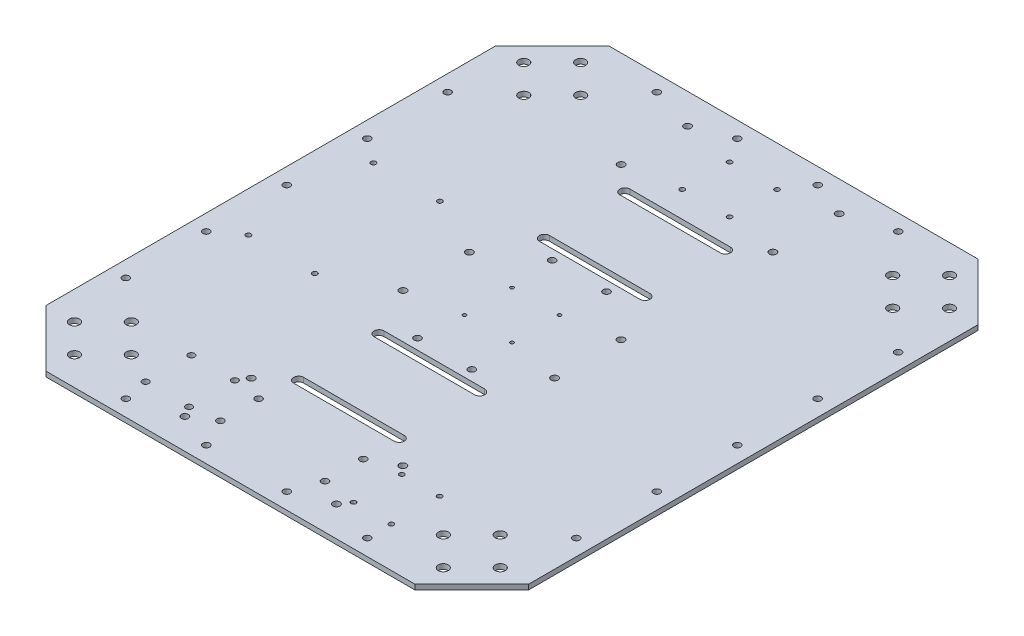
SolidWorks part; units mm, degrees
ref_plane "Front Plane" through (0, 0, 0) normal (0, 0, 1) x (1, 0, 0)
ref_plane "Top Plane" through (0, 0, 0) normal (0, 1, 0) x (1, 0, 0)
ref_plane "Right Plane" through (0, 0, 0) normal (1, 0, 0) x (0, 0, -1)
sketch "Sketch1" plane through (0, 0, 0) normal (0, 1, 0) x (1, 0, 0)
  line L0 (-121.2861, 87.138) -> (-85.365, 123.059)
  line L1 (-121.2861, 123.059) -> (183.5139, 123.059)
  line L2 (-121.2861, 123.059) -> (-121.2861, -232.541)
  line L3 (-121.2861, -232.541) -> (183.5139, -232.541)
  line L4 (183.5139, 123.059) -> (183.5139, -232.541)
  line L5 (31.1139, 95.069) -> (31.1139, -294.9418) construction
  line L6 (-146.0448, -54.741) -> (218.038, -54.741) construction
  line L7 (183.5139, 87.138) -> (147.5929, 123.059)
  line L8 (183.5139, -196.62) -> (147.5929, -232.541)
  line L9 (-121.2861, -196.62) -> (-85.365, -232.541)
  circle A0 centre (-16.7651, 104.009) radius 2.2225
  circle A1 centre (78.9929, 104.009) radius 2.2225
  circle A2 centre (-16.7651, 62.099) radius 2.2225
  circle A3 centre (78.9929, 62.099) radius 2.2225
  circle A4 centre (-16.7651, -171.581) radius 2.2225
  circle A5 centre (78.9929, -171.581) radius 2.2225
  circle A6 centre (78.9929, -213.491) radius 2.2225
  circle A7 centre (-16.7651, -213.491) radius 2.2225
  circle A8 centre (-16.7651, -33.786) radius 2.2225
  circle A9 centre (78.9929, -33.786) radius 2.2225
  circle A10 centre (78.9929, -75.696) radius 2.2225
  circle A11 centre (-16.7651, -75.696) radius 2.2225
  point P8 (31.1139, 123.059)
  point P11 (-121.2861, -54.741)
  dimension "D6" = 95.758
  dimension "D13" = 4.445
  dimension "D1" = 304.8
  dimension "D2" = 355.6
  dimension "D3" = 45
  dimension "D4" = 50.8
  dimension "D5" = 41.91
  dimension "D7" = 104.521
  dimension "D8" = 19.05
  dimension "D9" = 41.91
  dimension "D10" = 20.955
  dimension "D11" = 95.758
  dimension "D12" = 47.879
extrude "Boss-Extrude1" add sketch "Sketch1" along normal blind 3.175 contours L2 L9 L3 L8 L4 L7 L1 L0 region at (31.1139, 0, 54.741)
sketch "Sketch2" plane through (0, 3.175, 0) normal (0, 1, 0) x (1, 0, 0)
  line L0 (31.1139, 123.059) -> (31.1139, -287.8465) construction
  line L1 (-85.365, 123.059) -> (147.5929, 123.059) construction
  line L2 (183.5139, -54.741) -> (-158.2106, -54.741) construction
  line L3 (183.5139, 87.138) -> (183.5139, -196.62) construction
  circle A0 centre (13.8419, -12.069) radius 2.159
  circle A1 centre (48.1319, -12.069) radius 2.159
  circle A2 centre (13.8419, -97.159) radius 2.159
  circle A3 centre (48.1319, -97.159) radius 2.159
  dimension "D5" = 4.318
  dimension "D6" = 4.318
  dimension "D7" = 4.318
  dimension "D8" = 4.318
  dimension "D1" = 17.272
  dimension "D2" = 34.29
  dimension "D3" = 85.09
  dimension "D4" = 42.672
extrude "Cut-Extrude1" cut sketch "Sketch2" against normal through all
sketch "Sketch4" plane through (0, 3.175, 0) normal (0, 1, 0) x (1, 0, 0)
  line L0 (-0.6361, 48.256) -> (62.8639, 48.256) construction
  line L1 (-0.6361, 51.431) -> (62.8639, 51.431)
  line L2 (-0.6361, 45.081) -> (62.8639, 45.081)
  line L3 (-0.6361, -2.544) -> (62.8639, -2.544) construction
  line L4 (-0.6361, 0.631) -> (62.8639, 0.631)
  line L5 (-0.6361, -5.719) -> (62.8639, -5.719)
  line L6 (31.1139, 123.059) -> (31.1139, -75.2432) construction
  line L7 (-85.365, 123.059) -> (147.5929, 123.059) construction
  line L8 (-121.2861, -54.741) -> (257.7387, -54.741) construction
  line L9 (-121.2861, 87.138) -> (-121.2861, -196.62) construction
  line L10 (31.1139, -232.541) -> (31.1139, -34.2388) construction
  line L11 (-0.6361, -106.938) -> (62.8639, -106.938) construction
  line L12 (-0.6361, -110.113) -> (62.8639, -110.113)
  line L13 (-0.6361, -103.763) -> (62.8639, -103.763)
  line L14 (-0.6361, -157.738) -> (62.8639, -157.738) construction
  line L15 (-0.6361, -160.913) -> (62.8639, -160.913)
  line L16 (-0.6361, -154.563) -> (62.8639, -154.563)
  arc A0 (-0.6361, 51.431) -> (-0.6361, 45.081) centre (-0.6361, 48.256) ccw
  arc A1 (62.8639, 45.081) -> (62.8639, 51.431) centre (62.8639, 48.256) ccw
  arc A2 (-0.6361, 0.631) -> (-0.6361, -5.719) centre (-0.6361, -2.544) ccw
  arc A3 (62.8639, -5.719) -> (62.8639, 0.631) centre (62.8639, -2.544) ccw
  circle A4 centre (48.1319, -12.069) radius 2.159 construction
  arc A5 (-0.6361, -110.113) -> (-0.6361, -103.763) centre (-0.6361, -106.938) cw
  arc A6 (62.8639, -103.763) -> (62.8639, -110.113) centre (62.8639, -106.938) cw
  arc A7 (-0.6361, -160.913) -> (-0.6361, -154.563) centre (-0.6361, -157.738) cw
  arc A8 (62.8639, -154.563) -> (62.8639, -160.913) centre (62.8639, -157.738) cw
  point P2 (31.1139, 48.256)
  point P7 (31.1139, -2.544)
  point P28 (31.1139, -106.938)
  point P35 (31.1139, -157.738)
  dimension "D1" = 63.5
  dimension "D2" = 63.5
  dimension "D3" = 6.35
  dimension "D4" = 6.35
  dimension "D5" = 44.45
  dimension "D6" = 6.35
extrude "Cut-Extrude2" cut sketch "Sketch4" against normal through all
sketch "Sketch7" plane through (0, 3.175, 0) normal (0, 1, 0) x (1, 0, 0)
  line L0 (31.1139, 123.059) -> (31.1139, -19.2461) construction
  line L3 (-85.365, 123.059) -> (147.5929, 123.059) construction
  circle A0 centre (16.1279, 67.687) radius 1.524
  circle A1 centre (46.0999, 67.687) radius 1.524
  circle A2 centre (16.1279, 97.659) radius 1.524
  circle A3 centre (46.0999, 97.659) radius 1.524
  dimension "D1" = 3.048
  dimension "D2" = 3.048
  dimension "D4" = 14.986
  dimension "D3" = 29.972
  dimension "D5" = 25.4
extrude "Cut-Extrude3" cut sketch "Sketch7" against normal through all
sketch "Sketch8" plane through (0, 3.175, 0) normal (0, 1, 0) x (1, 0, 0)
  line L0 (-85.365, -232.541) -> (147.5929, -232.541) construction
  line L1 (183.5139, 87.138) -> (183.5139, -196.62) construction
  circle A0 centre (83.4379, -207.141) radius 1.524
  circle A1 centre (83.4379, -176.661) radius 1.524
  circle A2 centre (107.3139, -207.141) radius 1.524
  circle A3 centre (107.3139, -176.661) radius 1.524
  point P10 (0, 0)
  dimension "D1" = 3.048
  dimension "D2" = 30.48
  dimension "D3" = 23.876
  dimension "D4" = 25.4
  dimension "D5" = 76.2
extrude "Cut-Extrude4" cut sketch "Sketch8" against normal through all and the other way through all
sketch "Sketch9" plane through (0, 0, 0) normal (0, -1, 0) x (-1, 0, 0)
  line L0 (85.365, -232.541) -> (-147.5929, -232.541) construction
  line L1 (121.2861, 87.138) -> (121.2861, -196.62) construction
  circle A0 centre (48.1341, -206.887) radius 2.032
  circle A1 centre (20.7021, -206.887) radius 2.032
  circle A2 centre (48.1341, -177.931) radius 2.032
  circle A3 centre (20.7021, -177.931) radius 2.032
  dimension "D1" = 4.064
  dimension "D2" = 27.432
  dimension "D3" = 28.956
  dimension "D4" = 25.654
  dimension "D5" = 73.152
extrude "Cut-Extrude5" cut sketch "Sketch9" against normal through all
sketch "Sketch10" plane through (0, 0, 0) normal (0, -1, 0) x (1, 0, 0)
  line L0 (-85.365, 232.541) -> (147.5929, 232.541) construction
  line L1 (183.5139, -87.138) -> (183.5139, 196.62) construction
  circle A0 centre (-3.1761, 204.601) radius 2.159
  circle A1 centre (62.8639, 204.601) radius 2.159
  circle A2 centre (-3.1761, 180.471) radius 2.159
  circle A3 centre (62.8639, 180.471) radius 2.159
  dimension "D1" = 4.318
  dimension "D2" = 66.04
  dimension "D4" = 27.94
  dimension "D6" = 4.318
  dimension "D7" = 4.318
  dimension "D8" = 4.318
  dimension "D3" = 24.13
  dimension "D5" = 120.65
extrude "Cut-Extrude6" cut sketch "Sketch10" against normal through all
sketch "Sketch12" plane through (0, 0, 0) normal (0, -1, 0) x (1, 0, 0)
  line L0 (-121.2861, 54.741) -> (204.2138, 54.741) construction
  line L1 (-121.2861, -87.138) -> (-121.2861, 196.62) construction
  circle A0 centre (-95.8861, 94.216) radius 1.575
  circle A1 centre (-95.8861, 15.266) radius 1.575
  circle A2 centre (-53.9361, 15.266) radius 1.575
  circle A3 centre (-53.9361, 94.216) radius 1.575
  dimension "D1" = 3.15
  dimension "D2" = 3.15
  dimension "D3" = 3.15
  dimension "D4" = 3.15
  dimension "D5" = 78.95
  dimension "D6" = 39.475
  dimension "D7" = 41.95
  dimension "D8" = 25.4
extrude "Cut-Extrude7" cut sketch "Sketch12" against normal through all
sketch "Sketch13" plane through (0, 0, 0) normal (0, -1, 0) x (1, 0, 0)
  line L0 (31.1139, -123.059) -> (31.1139, 261.4711) construction
  line L1 (-85.365, -123.059) -> (147.5929, -123.059) construction
  line L2 (-121.2861, 54.741) -> (239.2508, 54.741) construction
  line L3 (-121.2861, -87.138) -> (-121.2861, 196.62) construction
  circle A0 centre (16.1139, 69.741) radius 1.1
  circle A1 centre (16.1139, 39.741) radius 1.1
  circle A2 centre (46.1139, 39.741) radius 1.1
  circle A3 centre (46.1139, 69.741) radius 1.1
  dimension "D1" = 2.2
  dimension "D2" = 2.2
  dimension "D3" = 30
  dimension "D4" = 15
  dimension "D5" = 15
extrude "Cut-Extrude8" cut sketch "Sketch13" against normal through all
sketch "Sketch14" plane through (0, 0, 0) normal (0, -1, 0) x (1, 0, 0)
  line L0 (31.1139, 232.541) -> (31.1139, -154.5354) construction
  line L1 (-85.365, 232.541) -> (147.5929, 232.541) construction
  line L2 (-121.2861, 54.741) -> (331.9066, 54.741) construction
  line L3 (-121.2861, -87.138) -> (-121.2861, 196.62) construction
  line L4 (-85.365, 214.5805) -> (-103.3255, 196.62) construction
  line L5 (-103.3255, 196.62) -> (-85.365, 178.6595) construction
  line L6 (-85.365, 178.6595) -> (-67.4045, 196.62) construction
  line L7 (-67.4045, 196.62) -> (-85.365, 214.5805) construction
  line L8 (-121.2861, 196.62) -> (-85.365, 232.541) construction
  line L9 (-103.3255, 214.5805) -> (-48.3665, 159.6215) construction
  circle A0 centre (-103.3255, 196.62) radius 3.175
  circle A1 centre (-85.365, 214.5805) radius 3.175
  circle A2 centre (-85.365, 178.6595) radius 3.175
  circle A3 centre (-67.4045, 196.62) radius 3.175
  circle A4 centre (129.6324, 196.62) radius 3.175
  circle A5 centre (147.5929, 178.6595) radius 3.175
  circle A6 centre (165.5534, 196.62) radius 3.175
  circle A7 centre (147.5929, 214.5805) radius 3.175
  circle A8 centre (-85.365, -105.0985) radius 3.175
  circle A9 centre (-103.3255, -87.138) radius 3.175
  circle A10 centre (-85.365, -69.1774) radius 3.175
  circle A11 centre (-67.4045, -87.138) radius 3.175
  circle A12 centre (165.5534, -87.138) radius 3.175
  circle A13 centre (147.5929, -69.1774) radius 3.175
  circle A14 centre (147.5929, -105.0985) radius 3.175
  circle A15 centre (129.6324, -87.138) radius 3.175
  dimension "D3" = 6.35
  dimension "D4" = 6.35
  dimension "D5" = 6.35
  dimension "D6" = 6.35
  dimension "D2" = 12.7
  dimension "D7" = 90
  dimension "D8" = 25.4
  dimension "D9" = 25.4
  dimension "D10" = 12.7
  dimension "D11" = 90
extrude "Cut-Extrude9" cut sketch "Sketch14" against normal through all
sketch "Sketch15" plane through (0, 0, 0) normal (0, -1, 0) x (1, 0, 0)
  line L0 (31.1139, 232.541) -> (31.1139, 125.875) construction
  line L1 (-85.365, 232.541) -> (147.5929, 232.541) construction
  line L2 (-121.2861, 54.741) -> (75.4631, 54.741) construction
  line L3 (-121.2861, -87.138) -> (-121.2861, 196.62) construction
  circle A0 centre (5.7139, 222.381) radius 2.159
  circle A1 centre (-45.0861, 222.381) radius 2.159
  circle A2 centre (-111.1261, 54.741) radius 2.159
  circle A3 centre (-111.1261, 105.541) radius 2.159
  circle A4 centre (-111.1261, 156.341) radius 2.159
  circle A5 centre (173.3539, 156.341) radius 2.159
  circle A6 centre (173.3539, 105.541) radius 2.159
  circle A7 centre (173.3539, 54.741) radius 2.159
  circle A8 centre (107.3139, 222.381) radius 2.159
  circle A9 centre (56.5139, 222.381) radius 2.159
  circle A10 centre (56.5139, -112.899) radius 2.159
  circle A11 centre (107.3139, -112.899) radius 2.159
  circle A12 centre (173.3539, 3.941) radius 2.159
  circle A13 centre (173.3539, -46.859) radius 2.159
  circle A14 centre (-111.1261, -46.859) radius 2.159
  circle A15 centre (-111.1261, 3.941) radius 2.159
  circle A16 centre (-45.0861, -112.899) radius 2.159
  circle A17 centre (5.7139, -112.899) radius 2.159
  point P18 (0, 0)
  dimension "D3" = 4.318
  dimension "D4" = 4.318
  dimension "D8" = 4.318
  dimension "D9" = 4.318
  dimension "D10" = 4.318
  dimension "D1" = 25.4
  dimension "D2" = 50.8
  dimension "D5" = 10.16
  dimension "D6" = 50.8
  dimension "D7" = 50.8
  dimension "D11" = 10.16
extrude "Cut-Extrude10" cut sketch "Sketch15" against normal through all
